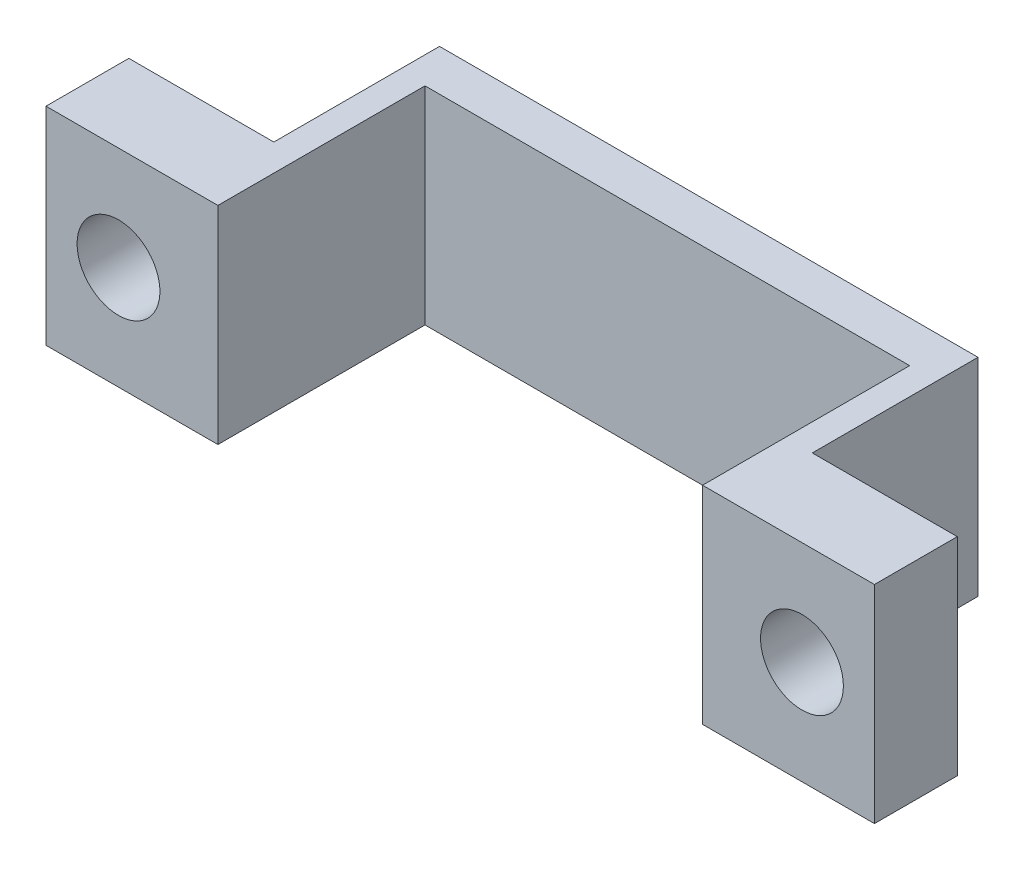
SolidWorks part; units mm, degrees
ref_plane "Спереди" through (0, 0, 0) normal (0, 0, 1) x (1, 0, 0)
ref_plane "Сверху" through (0, 0, 0) normal (0, 1, 0) x (1, 0, 0)
ref_plane "Справа" through (0, 0, 0) normal (1, 0, 0) x (0, 0, -1)
sketch "Эскиз1" plane through (0, 0, 0) normal (0, 1, 0) x (1, 0, 0)
  line L0 (-13, 2) -> (13, 2)
  line L1 (13, 2) -> (13, -6)
  line L2 (-13, 2) -> (-13, -6)
  line L3 (13, -6) -> (20, -6)
  line L4 (-13, -6) -> (-20, -6)
  line L5 (20, -6) -> (20, -10)
  line L6 (-20, -6) -> (-20, -10)
  line L7 (-20, -10) -> (-11.7, -10)
  line L8 (20, -10) -> (11.7, -10)
  line L9 (11.7, -10) -> (11.7, 0)
  line L10 (-11.7, -10) -> (-11.7, 0)
  line L11 (-11.7, 0) -> (11.7, 0)
  line L12 (15.85, -7.2854) -> (15.85, -8.9156) construction
  line L13 (-15.85, -7.2854) -> (-15.85, -9.2854) construction
  point P12 (0, 0)
  dimension "D1" = 26
  dimension "D2" = 8
  dimension "D3" = 8
  dimension "D4" = 7
  dimension "D5" = 7
  dimension "D6" = 4
  dimension "D7" = 4
  dimension "D8" = 8.3
  dimension "D9" = 8.3
  dimension "D10" = 2
  dimension "D11" = 4.15
  dimension "D12" = 2
  dimension "D13" = 4.15
  dimension "D14" = 31.7
extrude "Бобышка-Вытянуть1" add sketch "Эскиз1" along normal blind 10
ref_plane "Плоскость1" through (0, 0, 0) normal (-1, 0, 0) x (0, 0, 1)
sketch "Эскиз3" plane through (0, 0, 6) normal (0, 0, -1) x (-1, 0, 0)
  line L0 (20, 5) -> (-20, 5) construction
  line L1 (20, 10) -> (20, 0) construction
  line L2 (-20, 10) -> (-20, 0) construction
  line L3 (16.5, 10) -> (16.5, 0) construction
  line L4 (13, 10) -> (20, 10) construction
  line L5 (13, 0) -> (20, 0) construction
  circle A0 centre (16.5, 5) radius 2
  dimension "D1" = 4
extrude "Вырез-Вытянуть2" cut sketch "Эскиз3" against normal blind 4
mirror "Зеркальное отражение1" about plane through (0, 0, 0) normal (-1, 0, 0) of "Вырез-Вытянуть2"
